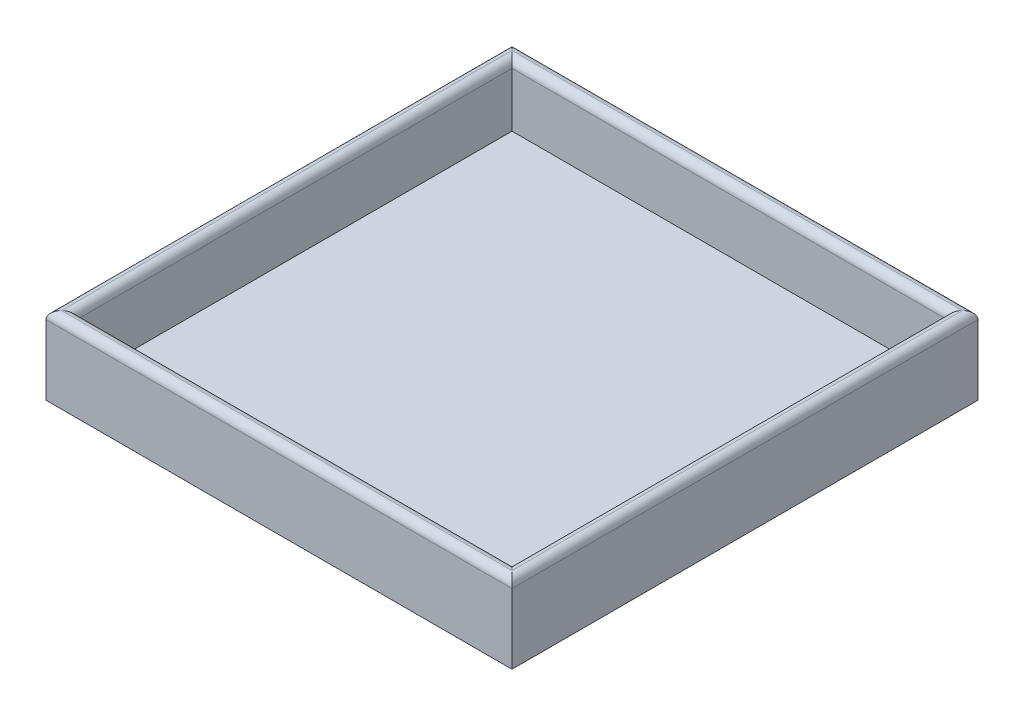
SolidWorks part; units mm, degrees
ref_plane "Front Plane" through (0, 0, 0) normal (0, 0, 1) x (1, 0, 0)
ref_plane "Top Plane" through (0, 0, 0) normal (0, 1, 0) x (1, 0, 0)
ref_plane "Right Plane" through (0, 0, 0) normal (1, 0, 0) x (0, 0, -1)
sketch "Sketch1" plane through (0, 0, 0) normal (0, 1, 0) x (1, 0, 0)
  line L1 (0, 0) -> (300, 0)
  line L2 (0, 0) -> (0, 300)
  line L3 (0, 300) -> (300, 300)
  line L4 (300, 0) -> (300, 300)
extrude "Boss-Extrude1" add sketch "Sketch1" along normal blind 50 contours L1 L4 L3 L2
sketch "Sketch2" plane through (0, 50, 0) normal (0, 1, 0) x (1, 0, 0)
  line L8 (10, 290) -> (10, 10)
  line L9 (10, 10) -> (290, 10)
  line L10 (290, 10) -> (290, 290)
  line L11 (290, 290) -> (10, 290)
  line L12 (10, 290) -> (10, 10)
  line L13 (10, 10) -> (290, 10)
  line L14 (290, 10) -> (290, 290)
  line L15 (290, 290) -> (10, 290)
  dimension "D1" = 10
extrude "Cut-Extrude1" cut sketch "Sketch2" against normal blind 40 contours L14 L15 L12 L13 | L12 L13 L14 L15 region at (150, 50, -150)
fillet "Fillet1" radius 5 8 edges at (150, 50, -300) (300, 50, -150) (150, 50, 0) (0, 50, -150) (290, 50, -150) (150, 50, -290) (10, 50, -150) (150, 50, -10)
